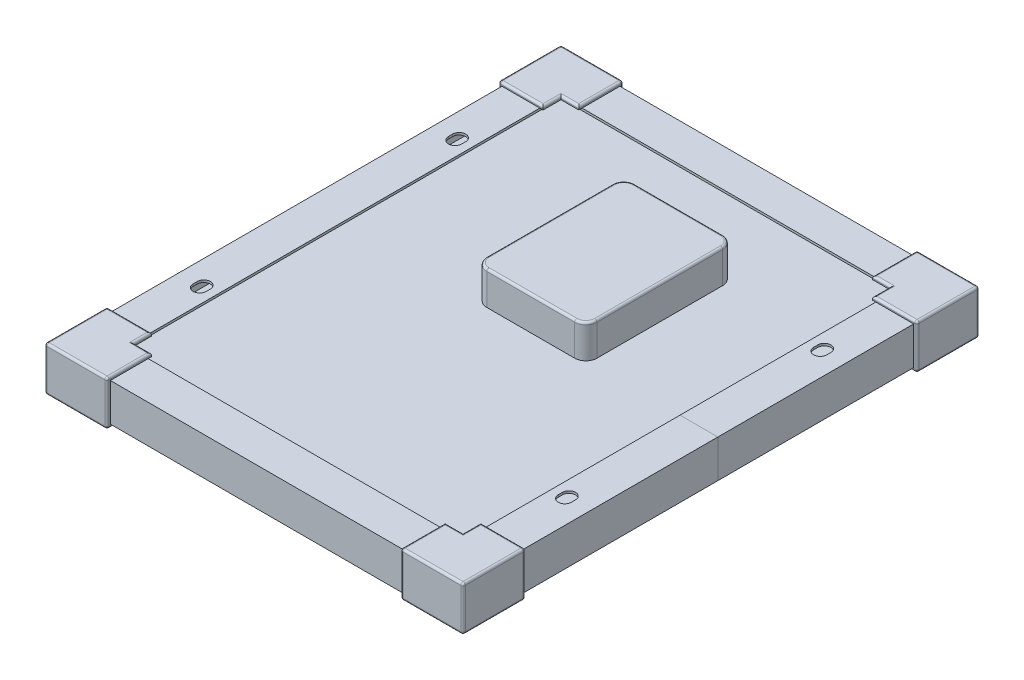
SolidWorks part; units mm, degrees
note: The reader was unsure of these and kept them because the rebuilt part matched: shared geometry of "Esquisse4<3>".
ref_plane "Plan de face" through (0, 0, 0) normal (0, 0, 1) x (1, 0, 0)
ref_plane "Plan de dessus" through (0, 0, 0) normal (0, 1, 0) x (1, 0, 0)
ref_plane "Plan de droite" through (0, 0, 0) normal (1, 0, 0) x (0, 0, -1)
sketch "Esquisse1" plane through (0, 0, 0) normal (0, 1, 0) x (1, 0, 0)
  line L0 (-86.5, 108.5) -> (86.5, 108.5)
  line L1 (-92.5, -114.5) -> (92.5, -114.5)
  line L2 (-92.5, -114.5) -> (-92.5, 114.5)
  line L3 (-92.5, 114.5) -> (92.5, 114.5)
  line L4 (92.5, -114.5) -> (92.5, 114.5)
  line L5 (-92.5, -114.5) -> (92.5, 114.5) construction
  line L6 (-92.5, 114.5) -> (92.5, -114.5) construction
  line L7 (86.5, -108.5) -> (86.5, 108.5)
  line L8 (-86.5, -108.5) -> (86.5, -108.5)
  line L9 (-86.5, -108.5) -> (-86.5, 108.5)
  line L10 (75.5, -97.5) -> (75.5, 97.5)
  line L11 (-75.5, 97.5) -> (75.5, 97.5)
  line L12 (-75.5, -97.5) -> (-75.5, 97.5)
  line L13 (-75.5, -97.5) -> (75.5, -97.5)
  line L14 (91.5, -113.5) -> (91.5, 113.5)
  line L15 (-91.5, 113.5) -> (91.5, 113.5)
  line L16 (-91.5, -113.5) -> (-91.5, 113.5)
  line L17 (-91.5, -113.5) -> (91.5, -113.5)
  point P0 (0, 0)
  dimension "D1" = 185
  dimension "D2" = 229
  dimension "D3" = 6
  dimension "D4" = 17
  dimension "D5" = 1
sketch "Esquisse2" plane through (0, 0, 0) normal (0, 0, 1) x (1, 0, 0)
  line L0 (86.5, 0) -> (92.5, 0)
  line L2 (-92.5, 0) -> (92.5, 0) construction
  line L3 (92.5, 0) -> (92.5, 17)
  line L4 (92.5, 17) -> (75.5, 17)
  line L5 (75.5, 17) -> (75.5, 16)
  line L6 (75.5, 16) -> (91.5, 16)
  line L7 (91.5, 16) -> (91.5, 1)
  line L8 (91.5, 1) -> (86.5, 1)
  line L9 (86.5, 1) -> (86.5, 0)
  dimension "D1" = 1
  dimension "D2" = 17
  dimension "D3" = 1
  dimension "D4" = 1
  dimension "D5" = 17
  dimension "D6" = 6
sweep "Balayage1" add profiles "Esquisse2" path "Esquisse1"
sketch "Esquisse3" plane through (0, 17, 0) normal (0, 1, 0) x (1, 0, 0)
  line L0 (-92.5, 0) -> (-75.5, 0) construction
  line L1 (-92.5, -114.5) -> (-92.5, 114.5) construction
  line L2 (-75.5, -97.5) -> (-75.5, 97.5) construction
  line L3 (-75.5, 0) -> (0, 0) construction
  line L4 (0, 0) -> (75.5, 0) construction
  line L5 (92.5, 0) -> (75.5, 0) construction
  line L6 (75.5, 0) -> (75.5, -97.5) construction
  line L7 (75.5, 0) -> (92.5, 0) construction
  line L8 (0, 114.5) -> (0, -114.5) construction
  line L9 (-92.5, 114.5) -> (92.5, 114.5) construction
  line L10 (92.5, -114.5) -> (-92.5, -114.5) construction
  line L11 (-82.05, 58.3) -> (-82.05, 56.45) construction
  line L12 (-79.1, 58.3) -> (-79.1, 56.45)
  line L13 (-85, 58.3) -> (-85, 56.45)
  line L14 (-82.05, 61.25) -> (-82.05, 53.5) construction
  line L15 (-85, 57.375) -> (-79.1, 57.375)
  line L16 (82.05, 61.25) -> (82.05, 53.5) construction
  line L17 (85, 57.375) -> (79.1, 57.375)
  line L18 (82.05, 58.3) -> (82.05, 56.45) construction
  line L19 (79.1, 58.3) -> (79.1, 56.45)
  line L20 (85, 58.3) -> (85, 56.45)
  line L21 (82.05, -61.25) -> (82.05, -53.5) construction
  line L22 (-82.05, -61.25) -> (-82.05, -53.5) construction
  line L23 (85, -57.375) -> (79.1, -57.375)
  line L24 (-85, -57.375) -> (-79.1, -57.375)
  line L25 (82.05, -58.3) -> (82.05, -56.45) construction
  line L26 (79.1, -58.3) -> (79.1, -56.45)
  line L27 (85, -58.3) -> (85, -56.45)
  line L28 (-82.05, -58.3) -> (-82.05, -56.45) construction
  line L29 (-79.1, -58.3) -> (-79.1, -56.45)
  line L30 (-85, -58.3) -> (-85, -56.45)
  arc A0 (-79.1, 58.3) -> (-85, 58.3) centre (-82.05, 58.3) ccw
  arc A1 (-85, 56.45) -> (-79.1, 56.45) centre (-82.05, 56.45) ccw
  arc A2 (79.1, 58.3) -> (85, 58.3) centre (82.05, 58.3) cw
  arc A3 (85, 56.45) -> (79.1, 56.45) centre (82.05, 56.45) cw
  arc A4 (79.1, -58.3) -> (85, -58.3) centre (82.05, -58.3) ccw
  arc A5 (85, -56.45) -> (79.1, -56.45) centre (82.05, -56.45) ccw
  arc A6 (-79.1, -58.3) -> (-85, -58.3) centre (-82.05, -58.3) cw
  arc A7 (-85, -56.45) -> (-79.1, -56.45) centre (-82.05, -56.45) cw
  point P23 (-82.05, 57.375)
  point P33 (-82.05, 57.375)
  point P37 (82.05, 57.375)
  point P40 (82.05, 57.375)
  point P55 (82.05, -57.375)
  point P60 (-82.05, -57.375)
  point P63 (-82.05, -57.375)
  dimension "D1" = 7.75
  dimension "D2" = 5.9
  dimension "D3" = 3.6
  dimension "D4" = 53.5
extrude "Enlèv. mat.-Extru.1" cut sketch "Esquisse3" against normal blind 10 contours A7 L30 L24 L29 | L12 A0 L13 L15 | L13 A1 L12 L15 | A2 L19 L17 L20 | A3 L20 L17 L19 | L27 A5 L26 L23 | L26 A4 L27 L23 | A6 L29 L24 L30
sketch "Esquisse4" plane through (0, 17, 0) normal (0, 1, 0) x (1, 0, 0)
  line L0 (-66, 116) -> (-94, 116)
  line L1 (-94, 116) -> (-94, 88)
  line L2 (-94, 88) -> (-74, 88)
  line L3 (-74, 88) -> (-74, 96)
  line L4 (-74, 96) -> (-66, 96)
  line L5 (-66, 96) -> (-66, 116)
  line L6 (-92.5, 114.5) -> (92.5, 114.5) construction
  line L9 (-75.5, -97.5) -> (-75.5, 97.5) construction
  line L10 (-92.5, -114.5) -> (-92.5, 114.5) construction
  line L11 (-92.5, 114.5) -> (-66, 114.5)
  line L12 (-92.5, 88) -> (-92.5, 114.5)
  line L13 (0, 114.5) -> (0, -114.5) construction
  line L14 (-92.5, 114.5) -> (92.5, 114.5) construction
  line L15 (92.5, -114.5) -> (-92.5, -114.5) construction
  line L16 (92.5, 88) -> (92.5, 114.5)
  line L17 (-92.5, -114.5) -> (-92.5, 114.5) construction
  line L18 (89.5, 0) -> (-92.5, 0) construction
  line L19 (86.5, 0) -> (92.5, 0) construction
  line L20 (92.5, 114.5) -> (66, 114.5)
  line L21 (66, 96) -> (66, 116)
  line L22 (74, 96) -> (66, 96)
  line L23 (74, 88) -> (74, 96)
  line L24 (94, 88) -> (74, 88)
  line L25 (94, 116) -> (94, 88)
  line L26 (66, 116) -> (94, 116)
  line L27 (66, -116) -> (94, -116)
  line L28 (94, -116) -> (94, -88)
  line L29 (94, -88) -> (74, -88)
  line L30 (74, -88) -> (74, -96)
  line L31 (74, -96) -> (66, -96)
  line L32 (66, -96) -> (66, -116)
  line L33 (92.5, -114.5) -> (66, -114.5)
  line L34 (92.5, -88) -> (92.5, -114.5)
  line L35 (-92.5, -88) -> (-92.5, -114.5)
  line L36 (-92.5, -114.5) -> (-66, -114.5)
  line L37 (-66, -96) -> (-66, -116)
  line L38 (-74, -96) -> (-66, -96)
  line L39 (-74, -88) -> (-74, -96)
  line L40 (-94, -88) -> (-74, -88)
  line L41 (-94, -116) -> (-94, -88)
  line L42 (-66, -116) -> (-94, -116)
  line M9 (-92.5, 114.5) -> (-92.5, -114.5)
  dimension "D1" = 90
  dimension "D2" = 28
  dimension "D3" = 28
  dimension "D4" = 8
  dimension "D5" = 8
  dimension "D6" = 1.5
  dimension "D7" = 1.5
extrude "Boss.-Extru.1" add sketch "Esquisse4" against normal up to surface (17 mm away) separate body contours L29 L34 L33 L32 L27 L28 | L42 L37 L36 L40 L41 M9 | L11 L5 L0 L1 L2 M9 | L26 L21 L20 L16 L24 L25 up to face at (0, 0, -111.5)
extrude "Boss.-Extru.2" add sketch "Esquisse4<3>" along normal blind 1.5 contours L41 L40 L39 L38 L37 L42 | L28 L29 L30 L31 L32 L27 | L25 L24 L23 L22 L21 L26 | L1 L2 L3 L4 L5 L0
sketch "Esquisse4<3>" plane through (0, 17, 0) normal (0, 1, 0) x (1, 0, 0) same geometry as "Esquisse4"
sketch "Esquisse5" plane through (0, 0, 0) normal (0, -1, 0) x (1, 0, 0)
  line L0 (-66, -116) -> (-94, -116) construction
  line L1 (-66, -116) -> (-94, -116)
  line L2 (-94, -116) -> (-94, -88) construction
  line L3 (-94, -116) -> (-94, -88)
  line L4 (-66, -96) -> (-66, -116) construction
  line L5 (-66, -116) -> (-66, -107)
  line L6 (-66, -107) -> (-85, -107)
  line L7 (-85, -107) -> (-85, -88)
  line L8 (-94, -88) -> (-74, -88) construction
  line L9 (-85, -88) -> (-94, -88)
  line L10 (-86.5, -108.5) -> (86.5, -108.5) construction
  line L11 (-86.5, 108.5) -> (-86.5, -108.5) construction
  line L12 (0, -114.5) -> (0, 0) construction
  line L13 (-66, -114.5) -> (66, -114.5) construction
  line L14 (0, 0) -> (-92.5, 0) construction
  line L15 (-92.5, 88) -> (-92.5, -88) construction
  line L16 (85, -88) -> (94, -88)
  line L17 (85, -107) -> (85, -88)
  line L18 (66, -107) -> (85, -107)
  line L19 (66, -116) -> (66, -107)
  line L20 (94, -116) -> (94, -88)
  line L21 (66, -116) -> (94, -116)
  line L22 (66, 116) -> (94, 116)
  line L23 (94, 116) -> (94, 88)
  line L24 (66, 116) -> (66, 107)
  line L25 (66, 107) -> (85, 107)
  line L26 (85, 107) -> (85, 88)
  line L27 (85, 88) -> (94, 88)
  line L28 (-85, 88) -> (-94, 88)
  line L29 (-85, 107) -> (-85, 88)
  line L30 (-66, 107) -> (-85, 107)
  line L31 (-66, 116) -> (-66, 107)
  line L32 (-94, 116) -> (-94, 88)
  line L33 (-66, 116) -> (-94, 116)
  dimension "D1" = 1.5
  dimension "D2" = 1.5
extrude "Boss.-Extru.3" add sketch "Esquisse5" along normal blind 1.5
fillet "Congé2" radius 1 66 edges at (-80, 18.5, 116) (-94, 8.5, 116) (-66, 18.5, 106) (-66, 8.5, 116) (-70, 18.5, 96) (-74, 18.5, 92) (-84, 18.5, 88) (-94, 18.5, 102) (-94, 8.5, 88) (-66, 8.5, -116) (-94, 8.5, -116) (-94, 8.5, -88) (66, 8.5, 116) (94, 8.5, 116) (94, 8.5, 88) (66, 8.5, -116) (94, 8.5, -116) (94, 8.5, -88) (80, 18.5, 116) (94, 18.5, 102) (84, 18.5, 88) (74, 18.5, 92) (70, 18.5, 96) (66, 18.5, 106) (80, 18.5, -116) (66, 18.5, -106) (70, 18.5, -96) (74, 18.5, -92) (84, 18.5, -88) (94, 18.5, -102) (-80, 18.5, -116) (-94, 18.5, -102) (-84, 18.5, -88) (-74, 18.5, -92) (-70, 18.5, -96) (-66, 18.5, -106) (0, 0, -108.5) (-66, -1.5, -111.5) (-75.5, -1.5, -107) (-85, -1.5, -97.5) (-89.5, -1.5, -88) (-94, -1.5, -102) (-80, -1.5, -116) (86.5, 0, -44) (85, -1.5, -97.5) (75.5, -1.5, -107) (66, -1.5, -111.5) (80, -1.5, -116) (94, -1.5, -102) (89.5, -1.5, -88) (0, 0, 108.5) (66, -1.5, 111.5) (75.5, -1.5, 107) (85, -1.5, 97.5) (89.5, -1.5, 88) (94, -1.5, 102) (80, -1.5, 116) (86.5, 0, 44) (-86.5, 0, 0) (86.5, 0.5, 0) (-85, -1.5, 97.5) (-75.5, -1.5, 107) (-66, -1.5, 111.5) (-80, -1.5, 116) (-94, -1.5, 102) (-89.5, -1.5, 88)
sketch "Esquisse6" plane through (0, 1, 0) normal (0, 1, 0) x (1, 0, 0)
  line L0 (-91.5, 113.5) -> (91.5, 113.5) construction
  line L1 (-91.5, 113.5) -> (91.5, 113.5)
  line L2 (-91.5, -113.5) -> (-91.5, 113.5) construction
  line L3 (-91.5, -113.5) -> (-91.5, 113.5)
  line L6 (91.5, -113.5) -> (-91.5, -113.5) construction
  line L7 (91.5, -113.5) -> (-91.5, -113.5)
  line L8 (91.5, -113.5) -> (91.5, 113.5)
  line L12 (57.95, 97) -> (40.3, 97) construction
  line L13 (57.95, 97) -> (57.95, 79.35) construction
  line L14 (57.95, 79.35) -> (40.3, 79.35) construction
  line L15 (40.3, 97) -> (40.3, 79.35) construction
  line L21 (38.3, 97) -> (20.65, 97) construction
  line L26 (77.6, 97) -> (59.95, 97) construction
  line L27 (77.6, 97) -> (77.6, 79.35) construction
  line L28 (77.6, 79.35) -> (59.95, 79.35) construction
  line L29 (59.95, 97) -> (59.95, 79.35) construction
  line L30 (38.3, 97) -> (38.3, 79.35) construction
  line L31 (38.3, 79.35) -> (20.65, 79.35) construction
  line L32 (20.65, 97) -> (20.65, 79.35) construction
  line L33 (18.65, 97) -> (1, 97) construction
  line L34 (18.65, 97) -> (18.65, 79.35) construction
  line L35 (18.65, 79.35) -> (1, 79.35) construction
  line L36 (1, 97) -> (1, 79.35) construction
  line L37 (-1, 97) -> (-18.65, 97) construction
  line L38 (-1, 97) -> (-1, 79.35) construction
  line L39 (-1, 79.35) -> (-18.65, 79.35) construction
  line L40 (-18.65, 97) -> (-18.65, 79.35) construction
  line L41 (-20.65, 97) -> (-38.3, 97) construction
  line L42 (-20.65, 97) -> (-20.65, 79.35) construction
  line L43 (-20.65, 79.35) -> (-38.3, 79.35) construction
  line L44 (-38.3, 97) -> (-38.3, 79.35) construction
  line L45 (-40.3, 97) -> (-57.95, 97) construction
  line L46 (-40.3, 97) -> (-40.3, 79.35) construction
  line L47 (-40.3, 79.35) -> (-57.95, 79.35) construction
  line L48 (-57.95, 97) -> (-57.95, 79.35) construction
  line L49 (-59.95, 97) -> (-77.6, 97) construction
  line L50 (-59.95, 97) -> (-59.95, 79.35) construction
  line L51 (-59.95, 79.35) -> (-77.6, 79.35) construction
  line L52 (-77.6, 97) -> (-77.6, 79.35) construction
  line L54 (57.95, 77.5) -> (40.3, 77.5) construction
  line L55 (57.95, 77.5) -> (57.95, 59.85) construction
  line L56 (57.95, 59.85) -> (40.3, 59.85) construction
  line L57 (40.3, 77.5) -> (40.3, 59.85) construction
  line L58 (38.3, 77.5) -> (20.65, 77.5) construction
  line L59 (77.6, 77.5) -> (59.95, 77.5) construction
  line L60 (77.6, 77.5) -> (77.6, 59.85) construction
  line L61 (77.6, 59.85) -> (59.95, 59.85) construction
  line L62 (59.95, 77.5) -> (59.95, 59.85) construction
  line L63 (38.3, 77.5) -> (38.3, 59.85) construction
  line L64 (38.3, 59.85) -> (20.65, 59.85) construction
  line L65 (20.65, 77.5) -> (20.65, 59.85) construction
  line L66 (18.65, 77.5) -> (1, 77.5) construction
  line L67 (18.65, 77.5) -> (18.65, 59.85) construction
  line L68 (18.65, 59.85) -> (1, 59.85) construction
  line L69 (1, 77.5) -> (1, 59.85) construction
  line L70 (-1, 77.5) -> (-18.65, 77.5) construction
  line L71 (-1, 77.5) -> (-1, 59.85) construction
  line L72 (-1, 59.85) -> (-18.65, 59.85) construction
  line L73 (-18.65, 77.5) -> (-18.65, 59.85) construction
  line L74 (-20.65, 77.5) -> (-38.3, 77.5) construction
  line L75 (-20.65, 77.5) -> (-20.65, 59.85) construction
  line L76 (-20.65, 59.85) -> (-38.3, 59.85) construction
  line L77 (-38.3, 77.5) -> (-38.3, 59.85) construction
  line L78 (-40.3, 77.5) -> (-57.95, 77.5) construction
  line L79 (-40.3, 77.5) -> (-40.3, 59.85) construction
  line L80 (-40.3, 59.85) -> (-57.95, 59.85) construction
  line L81 (-57.95, 77.5) -> (-57.95, 59.85) construction
  line L82 (-59.95, 77.5) -> (-77.6, 77.5) construction
  line L83 (-59.95, 77.5) -> (-59.95, 59.85) construction
  line L84 (-59.95, 59.85) -> (-77.6, 59.85) construction
  line L85 (-77.6, 77.5) -> (-77.6, 59.85) construction
  line L87 (57.95, 58) -> (40.3, 58) construction
  line L88 (57.95, 58) -> (57.95, 40.35) construction
  line L89 (57.95, 40.35) -> (40.3, 40.35) construction
  line L90 (40.3, 58) -> (40.3, 40.35) construction
  line L91 (38.3, 58) -> (20.65, 58) construction
  line L92 (77.6, 58) -> (59.95, 58) construction
  line L93 (77.6, 58) -> (77.6, 40.35) construction
  line L94 (77.6, 40.35) -> (59.95, 40.35) construction
  line L95 (59.95, 58) -> (59.95, 40.35) construction
  line L96 (38.3, 58) -> (38.3, 40.35) construction
  line L97 (38.3, 40.35) -> (20.65, 40.35) construction
  line L98 (20.65, 58) -> (20.65, 40.35) construction
  line L99 (18.65, 58) -> (1, 58) construction
  line L100 (18.65, 58) -> (18.65, 40.35) construction
  line L101 (18.65, 40.35) -> (1, 40.35) construction
  line L102 (1, 58) -> (1, 40.35) construction
  line L103 (-1, 58) -> (-18.65, 58) construction
  line L104 (-1, 58) -> (-1, 40.35) construction
  line L105 (-1, 40.35) -> (-18.65, 40.35) construction
  line L106 (-18.65, 58) -> (-18.65, 40.35) construction
  line L107 (-20.65, 58) -> (-38.3, 58) construction
  line L108 (-20.65, 58) -> (-20.65, 40.35) construction
  line L109 (-20.65, 40.35) -> (-38.3, 40.35) construction
  line L110 (-38.3, 58) -> (-38.3, 40.35) construction
  line L111 (-40.3, 58) -> (-57.95, 58) construction
  line L112 (-40.3, 58) -> (-40.3, 40.35) construction
  line L113 (-40.3, 40.35) -> (-57.95, 40.35) construction
  line L114 (-57.95, 58) -> (-57.95, 40.35) construction
  line L115 (-59.95, 58) -> (-77.6, 58) construction
  line L116 (-59.95, 58) -> (-59.95, 40.35) construction
  line L117 (-59.95, 40.35) -> (-77.6, 40.35) construction
  line L118 (-77.6, 58) -> (-77.6, 40.35) construction
  line L120 (57.95, 38.5) -> (40.3, 38.5) construction
  line L121 (57.95, 38.5) -> (57.95, 20.85) construction
  line L122 (57.95, 20.85) -> (40.3, 20.85) construction
  line L123 (40.3, 38.5) -> (40.3, 20.85) construction
  line L124 (38.3, 38.5) -> (20.65, 38.5) construction
  line L125 (77.6, 38.5) -> (59.95, 38.5) construction
  line L126 (77.6, 38.5) -> (77.6, 20.85) construction
  line L127 (77.6, 20.85) -> (59.95, 20.85) construction
  line L128 (59.95, 38.5) -> (59.95, 20.85) construction
  line L129 (38.3, 38.5) -> (38.3, 20.85) construction
  line L130 (38.3, 20.85) -> (20.65, 20.85) construction
  line L131 (20.65, 38.5) -> (20.65, 20.85) construction
  line L132 (18.65, 38.5) -> (1, 38.5) construction
  line L133 (18.65, 38.5) -> (18.65, 20.85) construction
  line L134 (18.65, 20.85) -> (1, 20.85) construction
  line L135 (1, 38.5) -> (1, 20.85) construction
  line L136 (-1, 38.5) -> (-18.65, 38.5) construction
  line L137 (-1, 38.5) -> (-1, 20.85) construction
  line L138 (-1, 20.85) -> (-18.65, 20.85) construction
  line L139 (-18.65, 38.5) -> (-18.65, 20.85) construction
  line L140 (-20.65, 38.5) -> (-38.3, 38.5) construction
  line L141 (-20.65, 38.5) -> (-20.65, 20.85) construction
  line L142 (-20.65, 20.85) -> (-38.3, 20.85) construction
  line L143 (-38.3, 38.5) -> (-38.3, 20.85) construction
  line L144 (-40.3, 38.5) -> (-57.95, 38.5) construction
  line L145 (-40.3, 38.5) -> (-40.3, 20.85) construction
  line L146 (-40.3, 20.85) -> (-57.95, 20.85) construction
  line L147 (-57.95, 38.5) -> (-57.95, 20.85) construction
  line L148 (-59.95, 38.5) -> (-77.6, 38.5) construction
  line L149 (-59.95, 38.5) -> (-59.95, 20.85) construction
  line L150 (-59.95, 20.85) -> (-77.6, 20.85) construction
  line L151 (-77.6, 38.5) -> (-77.6, 20.85) construction
  line L153 (57.95, 19) -> (40.3, 19) construction
  line L154 (57.95, 19) -> (57.95, 1.35) construction
  line L155 (57.95, 1.35) -> (40.3, 1.35) construction
  line L156 (40.3, 19) -> (40.3, 1.35) construction
  line L157 (38.3, 19) -> (20.65, 19) construction
  line L158 (77.6, 19) -> (59.95, 19) construction
  line L159 (77.6, 19) -> (77.6, 1.35) construction
  line L160 (77.6, 1.35) -> (59.95, 1.35) construction
  line L161 (59.95, 19) -> (59.95, 1.35) construction
  line L162 (38.3, 19) -> (38.3, 1.35) construction
  line L163 (38.3, 1.35) -> (20.65, 1.35) construction
  line L164 (20.65, 19) -> (20.65, 1.35) construction
  line L165 (18.65, 19) -> (1, 19) construction
  line L166 (18.65, 19) -> (18.65, 1.35) construction
  line L167 (18.65, 1.35) -> (1, 1.35) construction
  line L168 (1, 19) -> (1, 1.35) construction
  line L169 (-1, 19) -> (-18.65, 19) construction
  line L170 (-1, 19) -> (-1, 1.35) construction
  line L171 (-1, 1.35) -> (-18.65, 1.35) construction
  line L172 (-18.65, 19) -> (-18.65, 1.35) construction
  line L173 (-20.65, 19) -> (-38.3, 19) construction
  line L174 (-20.65, 19) -> (-20.65, 1.35) construction
  line L175 (-20.65, 1.35) -> (-38.3, 1.35) construction
  line L176 (-38.3, 19) -> (-38.3, 1.35) construction
  line L177 (-40.3, 19) -> (-57.95, 19) construction
  line L178 (-40.3, 19) -> (-40.3, 1.35) construction
  line L179 (-40.3, 1.35) -> (-57.95, 1.35) construction
  line L180 (-57.95, 19) -> (-57.95, 1.35) construction
  line L181 (-59.95, 19) -> (-77.6, 19) construction
  line L182 (-59.95, 19) -> (-59.95, 1.35) construction
  line L183 (-59.95, 1.35) -> (-77.6, 1.35) construction
  line L184 (-77.6, 19) -> (-77.6, 1.35) construction
  line L186 (57.95, -0.5) -> (40.3, -0.5) construction
  line L187 (57.95, -0.5) -> (57.95, -18.15) construction
  line L188 (57.95, -18.15) -> (40.3, -18.15) construction
  line L189 (40.3, -0.5) -> (40.3, -18.15) construction
  line L190 (38.3, -0.5) -> (20.65, -0.5) construction
  line L191 (77.6, -0.5) -> (59.95, -0.5) construction
  line L192 (77.6, -0.5) -> (77.6, -18.15) construction
  line L193 (77.6, -18.15) -> (59.95, -18.15) construction
  line L194 (59.95, -0.5) -> (59.95, -18.15) construction
  line L195 (38.3, -0.5) -> (38.3, -18.15) construction
  line L196 (38.3, -18.15) -> (20.65, -18.15) construction
  line L197 (20.65, -0.5) -> (20.65, -18.15) construction
  line L198 (18.65, -0.5) -> (1, -0.5) construction
  line L199 (18.65, -0.5) -> (18.65, -18.15) construction
  line L200 (18.65, -18.15) -> (1, -18.15) construction
  line L201 (1, -0.5) -> (1, -18.15) construction
  line L202 (-1, -0.5) -> (-18.65, -0.5) construction
  line L203 (-1, -0.5) -> (-1, -18.15) construction
  line L204 (-1, -18.15) -> (-18.65, -18.15) construction
  line L205 (-18.65, -0.5) -> (-18.65, -18.15) construction
  line L206 (-20.65, -0.5) -> (-38.3, -0.5) construction
  line L207 (-20.65, -0.5) -> (-20.65, -18.15) construction
  line L208 (-20.65, -18.15) -> (-38.3, -18.15) construction
  line L209 (-38.3, -0.5) -> (-38.3, -18.15) construction
  line L210 (-40.3, -0.5) -> (-57.95, -0.5) construction
  line L211 (-40.3, -0.5) -> (-40.3, -18.15) construction
  line L212 (-40.3, -18.15) -> (-57.95, -18.15) construction
  line L213 (-57.95, -0.5) -> (-57.95, -18.15) construction
  line L214 (-59.95, -0.5) -> (-77.6, -0.5) construction
  line L215 (-59.95, -0.5) -> (-59.95, -18.15) construction
  line L216 (-59.95, -18.15) -> (-77.6, -18.15) construction
  line L217 (-77.6, -0.5) -> (-77.6, -18.15) construction
  line L219 (57.95, -20) -> (40.3, -20) construction
  line L220 (57.95, -20) -> (57.95, -37.65) construction
  line L221 (57.95, -37.65) -> (40.3, -37.65) construction
  line L222 (40.3, -20) -> (40.3, -37.65) construction
  line L223 (38.3, -20) -> (20.65, -20) construction
  line L224 (77.6, -20) -> (59.95, -20) construction
  line L225 (77.6, -20) -> (77.6, -37.65) construction
  line L226 (77.6, -37.65) -> (59.95, -37.65) construction
  line L227 (59.95, -20) -> (59.95, -37.65) construction
  line L228 (38.3, -20) -> (38.3, -37.65) construction
  line L229 (38.3, -37.65) -> (20.65, -37.65) construction
  line L230 (20.65, -20) -> (20.65, -37.65) construction
  line L231 (18.65, -20) -> (1, -20) construction
  line L232 (18.65, -20) -> (18.65, -37.65) construction
  line L233 (18.65, -37.65) -> (1, -37.65) construction
  line L234 (1, -20) -> (1, -37.65) construction
  line L235 (-1, -20) -> (-18.65, -20) construction
  line L236 (-1, -20) -> (-1, -37.65) construction
  line L237 (-1, -37.65) -> (-18.65, -37.65) construction
  line L238 (-18.65, -20) -> (-18.65, -37.65) construction
  line L239 (-20.65, -20) -> (-38.3, -20) construction
  line L240 (-20.65, -20) -> (-20.65, -37.65) construction
  line L241 (-20.65, -37.65) -> (-38.3, -37.65) construction
  line L242 (-38.3, -20) -> (-38.3, -37.65) construction
  line L243 (-40.3, -20) -> (-57.95, -20) construction
  line L244 (-40.3, -20) -> (-40.3, -37.65) construction
  line L245 (-40.3, -37.65) -> (-57.95, -37.65) construction
  line L246 (-57.95, -20) -> (-57.95, -37.65) construction
  line L247 (-59.95, -20) -> (-77.6, -20) construction
  line L248 (-59.95, -20) -> (-59.95, -37.65) construction
  line L249 (-59.95, -37.65) -> (-77.6, -37.65) construction
  line L250 (-77.6, -20) -> (-77.6, -37.65) construction
  line L252 (57.95, -39.5) -> (40.3, -39.5) construction
  line L253 (57.95, -39.5) -> (57.95, -57.15) construction
  line L254 (57.95, -57.15) -> (40.3, -57.15) construction
  line L255 (40.3, -39.5) -> (40.3, -57.15) construction
  line L256 (38.3, -39.5) -> (20.65, -39.5) construction
  line L257 (77.6, -39.5) -> (59.95, -39.5) construction
  line L258 (77.6, -39.5) -> (77.6, -57.15) construction
  line L259 (77.6, -57.15) -> (59.95, -57.15) construction
  line L260 (59.95, -39.5) -> (59.95, -57.15) construction
  line L261 (38.3, -39.5) -> (38.3, -57.15) construction
  line L262 (38.3, -57.15) -> (20.65, -57.15) construction
  line L263 (20.65, -39.5) -> (20.65, -57.15) construction
  line L264 (18.65, -39.5) -> (1, -39.5) construction
  line L265 (18.65, -39.5) -> (18.65, -57.15) construction
  line L266 (18.65, -57.15) -> (1, -57.15) construction
  line L267 (1, -39.5) -> (1, -57.15) construction
  line L268 (-1, -39.5) -> (-18.65, -39.5) construction
  line L269 (-1, -39.5) -> (-1, -57.15) construction
  line L270 (-1, -57.15) -> (-18.65, -57.15) construction
  line L271 (-18.65, -39.5) -> (-18.65, -57.15) construction
  line L272 (-20.65, -39.5) -> (-38.3, -39.5) construction
  line L273 (-20.65, -39.5) -> (-20.65, -57.15) construction
  line L274 (-20.65, -57.15) -> (-38.3, -57.15) construction
  line L275 (-38.3, -39.5) -> (-38.3, -57.15) construction
  line L276 (-40.3, -39.5) -> (-57.95, -39.5) construction
  line L277 (-40.3, -39.5) -> (-40.3, -57.15) construction
  line L278 (-40.3, -57.15) -> (-57.95, -57.15) construction
  line L279 (-57.95, -39.5) -> (-57.95, -57.15) construction
  line L280 (-59.95, -39.5) -> (-77.6, -39.5) construction
  line L281 (-59.95, -39.5) -> (-59.95, -57.15) construction
  line L282 (-59.95, -57.15) -> (-77.6, -57.15) construction
  line L283 (-77.6, -39.5) -> (-77.6, -57.15) construction
  line L285 (57.95, -59) -> (40.3, -59) construction
  line L286 (57.95, -59) -> (57.95, -76.65) construction
  line L287 (57.95, -76.65) -> (40.3, -76.65) construction
  line L288 (40.3, -59) -> (40.3, -76.65) construction
  line L289 (38.3, -59) -> (20.65, -59) construction
  line L290 (77.6, -59) -> (59.95, -59) construction
  line L291 (77.6, -59) -> (77.6, -76.65) construction
  line L292 (77.6, -76.65) -> (59.95, -76.65) construction
  line L293 (59.95, -59) -> (59.95, -76.65) construction
  line L294 (38.3, -59) -> (38.3, -76.65) construction
  line L295 (38.3, -76.65) -> (20.65, -76.65) construction
  line L296 (20.65, -59) -> (20.65, -76.65) construction
  line L297 (18.65, -59) -> (1, -59) construction
  line L298 (18.65, -59) -> (18.65, -76.65) construction
  line L299 (18.65, -76.65) -> (1, -76.65) construction
  line L300 (1, -59) -> (1, -76.65) construction
  line L301 (-1, -59) -> (-18.65, -59) construction
  line L302 (-1, -59) -> (-1, -76.65) construction
  line L303 (-1, -76.65) -> (-18.65, -76.65) construction
  line L304 (-18.65, -59) -> (-18.65, -76.65) construction
  line L305 (-20.65, -59) -> (-38.3, -59) construction
  line L306 (-20.65, -59) -> (-20.65, -76.65) construction
  line L307 (-20.65, -76.65) -> (-38.3, -76.65) construction
  line L308 (-38.3, -59) -> (-38.3, -76.65) construction
  line L309 (-40.3, -59) -> (-57.95, -59) construction
  line L310 (-40.3, -59) -> (-40.3, -76.65) construction
  line L311 (-40.3, -76.65) -> (-57.95, -76.65) construction
  line L312 (-57.95, -59) -> (-57.95, -76.65) construction
  line L313 (-59.95, -59) -> (-77.6, -59) construction
  line L314 (-59.95, -59) -> (-59.95, -76.65) construction
  line L315 (-59.95, -76.65) -> (-77.6, -76.65) construction
  line L316 (-77.6, -59) -> (-77.6, -76.65) construction
  line L318 (57.95, -78.5) -> (40.3, -78.5) construction
  line L319 (57.95, -78.5) -> (57.95, -96.15) construction
  line L320 (57.95, -96.15) -> (40.3, -96.15) construction
  line L321 (40.3, -78.5) -> (40.3, -96.15) construction
  line L322 (38.3, -78.5) -> (20.65, -78.5) construction
  line L323 (77.6, -78.5) -> (59.95, -78.5) construction
  line L324 (77.6, -78.5) -> (77.6, -96.15) construction
  line L325 (77.6, -96.15) -> (59.95, -96.15) construction
  line L326 (59.95, -78.5) -> (59.95, -96.15) construction
  line L327 (38.3, -78.5) -> (38.3, -96.15) construction
  line L328 (38.3, -96.15) -> (20.65, -96.15) construction
  line L329 (20.65, -78.5) -> (20.65, -96.15) construction
  line L330 (18.65, -78.5) -> (1, -78.5) construction
  line L331 (18.65, -78.5) -> (18.65, -96.15) construction
  line L332 (18.65, -96.15) -> (1, -96.15) construction
  line L333 (1, -78.5) -> (1, -96.15) construction
  line L334 (-1, -78.5) -> (-18.65, -78.5) construction
  line L335 (-1, -78.5) -> (-1, -96.15) construction
  line L336 (-1, -96.15) -> (-18.65, -96.15) construction
  line L337 (-18.65, -78.5) -> (-18.65, -96.15) construction
  line L338 (-20.65, -78.5) -> (-38.3, -78.5) construction
  line L339 (-20.65, -78.5) -> (-20.65, -96.15) construction
  line L340 (-20.65, -96.15) -> (-38.3, -96.15) construction
  line L341 (-38.3, -78.5) -> (-38.3, -96.15) construction
  line L342 (-40.3, -78.5) -> (-57.95, -78.5) construction
  line L343 (-40.3, -78.5) -> (-40.3, -96.15) construction
  line L344 (-40.3, -96.15) -> (-57.95, -96.15) construction
  line L345 (-57.95, -78.5) -> (-57.95, -96.15) construction
  line L346 (-59.95, -78.5) -> (-77.6, -78.5) construction
  line L347 (-59.95, -78.5) -> (-59.95, -96.15) construction
  line L348 (-59.95, -96.15) -> (-77.6, -96.15) construction
  line L349 (-77.6, -78.5) -> (-77.6, -96.15) construction
  line L350 (-91.5, -133) -> (-91.5, 94) [skipped]
  line L351 (-91.5, -152.5) -> (-91.5, 74.5) [skipped]
  line L352 (-91.5, -172) -> (-91.5, 55) [skipped]
  line L353 (-91.5, -191.5) -> (-91.5, 35.5) [skipped]
  line L354 (-91.5, -211) -> (-91.5, 16) [skipped]
  line L355 (-91.5, -230.5) -> (-91.5, -3.5) [skipped]
  line L356 (-91.5, -250) -> (-91.5, -23) [skipped]
  line L357 (-91.5, -269.5) -> (-91.5, -42.5) [skipped]
  line L358 (-91.5, -289) -> (-91.5, -62) [skipped]
  point P4 (77.6, -113.5)
  point P6 (77.6, 113.5)
  point P7 (-77.6, -113.5)
  point P8 (-77.6, 113.5)
  point P9 (91.5, -97)
  point P10 (-91.5, -97)
  point P11 (-91.5, 97)
  point P12 (91.5, 97)
  dimension "D5" = 17.65
  dimension "D6" = 17.65
  dimension "D8" = 8
  dimension "D9" = 10
extrude "Boss.-Extru.8" add sketch "Esquisse6" along normal blind 6
sketch "Esquisse7" plane through (0, 1, 0) normal (0, -1, 0) x (1, 0, 0)
  line L1 (77.6, -97) -> (59.95, -97)
  line L2 (77.6, -97) -> (77.6, -79.35)
  line L3 (77.6, -79.35) -> (59.95, -79.35)
  line L4 (59.95, -97) -> (59.95, -79.35)
extrude "Boss.-Extru.9" add sketch "Esquisse7" along normal blind 0.1
pattern_linear "Répétition linéaire1" count 8 spacing 19.65 along (-1, 0, 0) count 10 spacing 19.65 along (0, 0, 1) of "Boss.-Extru.9"
sketch "Esquisse8" plane through (0, 7, 0) normal (0, 1, 0) x (1, 0, 0)
  line L0 (-66, 97.5) -> (66, 97.5) construction
  line L1 (-19.8245, 75) -> (19.6755, 75)
  line L2 (-24.8245, 70) -> (-24.8245, 13.5)
  line L3 (-19.8245, 8.5) -> (19.6755, 8.5)
  line L4 (24.6755, 70) -> (24.6755, 13.5)
  line L5 (-24.8245, 75) -> (24.6755, 8.5) construction
  line L6 (-24.8245, 8.5) -> (24.6755, 75) construction
  line L7 (-17.8245, 73) -> (17.6755, 73)
  line L8 (22.6755, 68) -> (22.6755, 15.5)
  line L9 (-17.8245, 10.5) -> (17.6755, 10.5)
  line L10 (-22.8245, 68) -> (-22.8245, 15.5)
  line L11 (-22.8245, 73) -> (-22.8245, 10.5) construction
  line L12 (-22.8245, 10.5) -> (22.6755, 10.5) construction
  line L13 (22.6755, 73) -> (22.6755, 10.5) construction
  line L14 (-22.8245, 73) -> (22.6755, 73) construction
  line L15 (-24.8245, 75) -> (24.6755, 75) construction
  line L16 (24.6755, 75) -> (24.6755, 8.5) construction
  line L17 (-24.8245, 75) -> (-24.8245, 8.5) construction
  line L18 (-24.8245, 8.5) -> (24.6755, 8.5) construction
  arc A0 (-22.8245, 15.5) -> (-17.8245, 10.5) centre (-17.8245, 15.5) ccw
  arc A1 (17.6755, 10.5) -> (22.6755, 15.5) centre (17.6755, 15.5) ccw
  arc A2 (22.6755, 68) -> (17.6755, 73) centre (17.6755, 68) ccw
  arc A3 (-22.8245, 68) -> (-17.8245, 73) centre (-17.8245, 68) cw
  arc A4 (19.6755, 75) -> (24.6755, 70) centre (19.6755, 70) cw
  arc A5 (-24.8245, 13.5) -> (-19.8245, 8.5) centre (-19.8245, 13.5) ccw
  arc A6 (-19.8245, 75) -> (-24.8245, 70) centre (-19.8245, 70) ccw
  arc A7 (19.6755, 8.5) -> (24.6755, 13.5) centre (19.6755, 13.5) ccw
  point P0 (-0.0745, 41.75)
  dimension "D5" = 5
  dimension "D1" = 66.5
  dimension "D2" = 49.5
  dimension "D3" = 22.5
  dimension "D4" = 2
extrude "Boss.-Extru.10" add sketch "Esquisse8" along normal blind 13
sketch "Esquisse9" plane through (0, 20, 0) normal (0, 1, 0) x (1, 0, 0)
  line L4 (19.6755, 75) -> (-19.8245, 75)
  line L5 (-24.8245, 70) -> (-24.8245, 13.5)
  line L6 (-19.8245, 8.5) -> (19.6755, 8.5)
  line L7 (24.6755, 13.5) -> (24.6755, 70)
  line L8 (19.6755, 75) -> (-19.8245, 75)
  line L9 (-24.8245, 70) -> (-24.8245, 13.5)
  line L10 (-19.8245, 8.5) -> (19.6755, 8.5)
  line L11 (24.6755, 13.5) -> (24.6755, 70)
  arc A4 (24.6755, 70) -> (19.6755, 75) centre (19.6755, 70) ccw
  arc A5 (-19.8245, 75) -> (-24.8245, 70) centre (-19.8245, 70) ccw
  arc A6 (-24.8245, 13.5) -> (-19.8245, 8.5) centre (-19.8245, 13.5) ccw
  arc A7 (19.6755, 8.5) -> (24.6755, 13.5) centre (19.6755, 13.5) ccw
  arc A8 (24.6755, 70) -> (19.6755, 75) centre (19.6755, 70) ccw
  arc A9 (-19.8245, 75) -> (-24.8245, 70) centre (-19.8245, 70) ccw
  arc A10 (-24.8245, 13.5) -> (-19.8245, 8.5) centre (-19.8245, 13.5) ccw
  arc A11 (19.6755, 8.5) -> (24.6755, 13.5) centre (19.6755, 13.5) ccw
  dimension "D1" = 0
extrude "Boss.-Extru.11" add sketch "Esquisse9" along normal blind 2
fillet "Congé3" radius 1 8 edges at (24.6755, 22, -41.75) (23.211, 22, -9.9645) (-0.0745, 22, -8.5) (-23.3601, 22, -9.9645) (-24.8245, 22, -41.75) (-23.3601, 22, -73.5355) (-0.0745, 22, -75) (23.211, 22, -73.5355)
